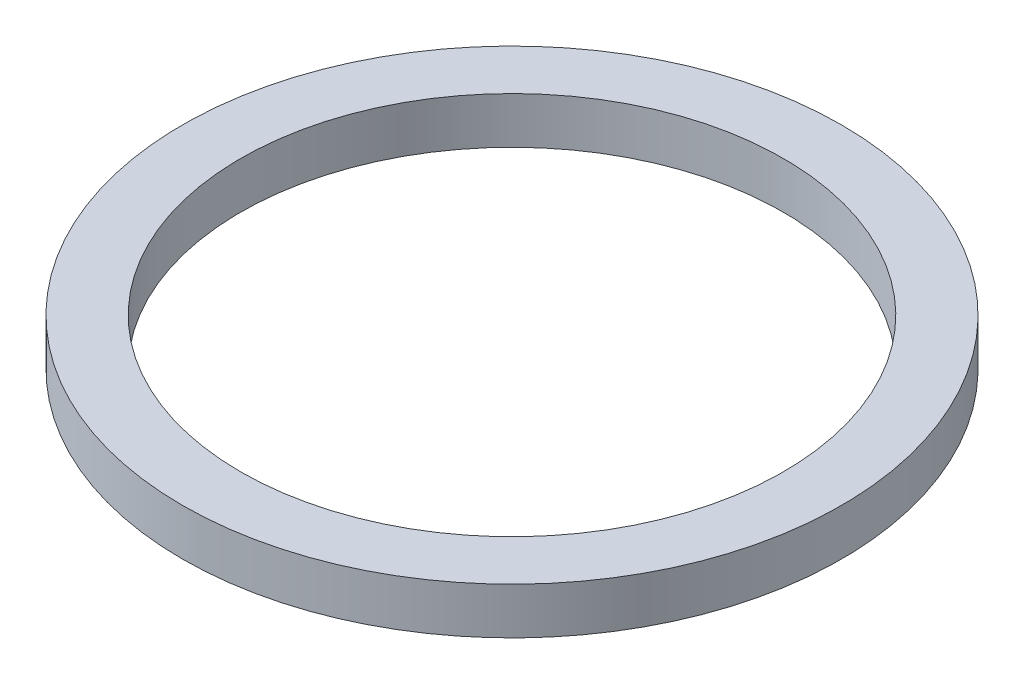
SolidWorks part; units mm, degrees
ref_plane "Front Plane" through (0, 0, 0) normal (0, 0, 1) x (1, 0, 0)
ref_plane "Top Plane" through (0, 0, 0) normal (0, 1, 0) x (1, 0, 0)
ref_plane "Right Plane" through (0, 0, 0) normal (1, 0, 0) x (0, 0, -1)
sketch "Sketch1" plane through (0, 0, 0) normal (0, 1, 0) x (1, 0, 0)
  circle A0 centre (0, 0) radius 42.5
  dimension "FLANGE_OD" = 85
extrude "Boss-Extrude1" add sketch "Sketch1" along normal blind 6
sketch "Sketch2" plane through (0, 0, 0) normal (0, 1, 0) x (1, 0, 0)
  circle A0 centre (0, 0) radius 35
  dimension "BORE_D" = 70
extrude "Cut-Extrude1" cut sketch "Sketch2" along normal through all
sketch "Sketch3" plane through (0, 6, 0) normal (0, 1, 0) x (1, 0, 0)
  circle A0 centre (0, 0) radius 18.8605 construction
  circle A1 centre (-18.8605, 0) radius 1.5
  dimension "BOLT_D" = 3
  dimension "BOLT_PCD" = 37.7211
extrude "Cut-Extrude2" cut sketch "Sketch3" against normal blind 3.8927 rebuild error yes
pattern_circular "CirPattern1" count 3 over 360 rebuild error yes
